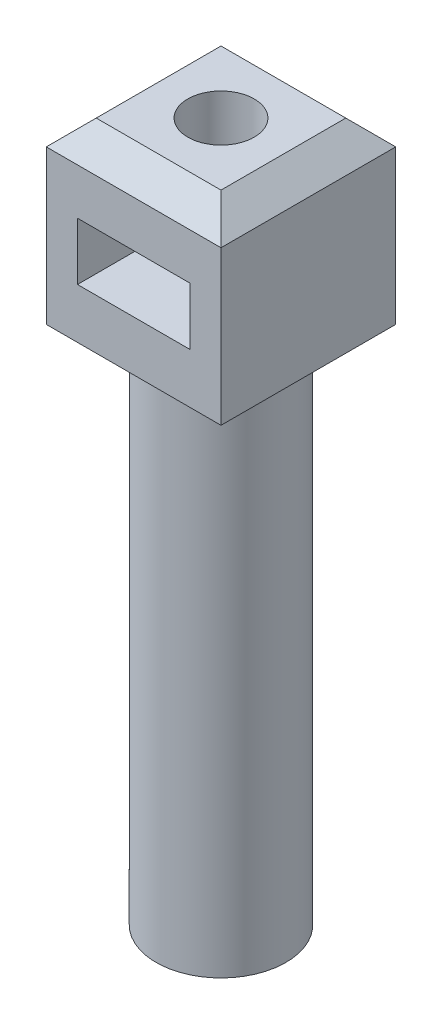
SolidWorks part; units mm, degrees
ref_plane "Front Plane" through (0, 0, 0) normal (0, 0, 1) x (1, 0, 0)
ref_plane "Top Plane" through (0, 0, 0) normal (0, 1, 0) x (1, 0, 0)
ref_plane "Right Plane" through (0, 0, 0) normal (1, 0, 0) x (0, 0, -1)
sketch "Sketch1" plane through (0, 0, 0) normal (0, 1, 0) x (1, 0, 0)
  circle A0 centre (0, 0) radius 6.604
  dimension "D1" = 13.208
extrude "Boss-Extrude1" add sketch "Sketch1" along normal blind 63.5
sketch "Sketch4" plane through (0, 0, 0) normal (0, -1, 0) x (1, 0, 0)
  line L1 (-12.7, -12.7) -> (12.7, -12.7)
  line L2 (-12.7, -12.7) -> (-12.7, 12.7)
  line L3 (-12.7, 12.7) -> (12.7, 12.7)
  line L4 (12.7, -12.7) -> (12.7, 12.7)
  line L5 (-12.7, -12.7) -> (12.7, 12.7) construction
  line L6 (-12.7, 12.7) -> (12.7, -12.7) construction
  point P0 (0, 0)
  dimension "D1" = 25.4
  dimension "D2" = 25.4
extrude "Boss-Extrude2" add sketch "Sketch4" along normal blind 1.27
ref_axis "Axis2" through (0, 63.5, 0) along (0, -1, 0)
ref_plane "Plane2" through (0, 50.8, 0) normal (0, 1, 0) x (1, 0, 0)
sketch "Sketch9" plane through (0, 50.8, 0) normal (0, 1, 0) x (1, 0, 0)
  line L1 (-8.89, -8.89) -> (8.89, -8.89)
  line L2 (-8.89, -8.89) -> (-8.89, 8.89)
  line L3 (-8.89, 8.89) -> (8.89, 8.89)
  line L4 (8.89, -8.89) -> (8.89, 8.89)
  line L5 (-8.89, -8.89) -> (8.89, 8.89) construction
  line L6 (-8.89, 8.89) -> (8.89, -8.89) construction
  point P0 (0, 0)
  dimension "D1" = 17.78
  dimension "D2" = 17.78
extrude "Boss-Extrude4" add sketch "Sketch9" along normal blind 20.32
sketch "Sketch10" plane through (0, 0, 8.89) normal (0, 0, 1) x (1, 0, 0)
  line L0 (0, 63.5) -> (0, 0) construction
  line L1 (-5.715, 58.039) -> (5.715, 58.039)
  line L2 (-5.715, 58.039) -> (-5.715, 63.881)
  line L3 (-5.715, 63.881) -> (5.715, 63.881)
  line L4 (5.715, 58.039) -> (5.715, 63.881)
  line L5 (-5.715, 58.039) -> (5.715, 63.881) construction
  line L6 (-5.715, 63.881) -> (5.715, 58.039) construction
  line L7 (-8.89, 71.12) -> (8.89, 71.12) construction
  line L8 (-8.89, 50.8) -> (8.89, 50.8) construction
  point P0 (0, 60.96)
  dimension "D1" = 11.43
  dimension "D2" = 5.842
  dimension "D3" = 7.239
  dimension "D4" = 7.239
extrude "Cut-Extrude2" cut sketch "Sketch10" against normal through all both and the other way through all
chamfer "Chamfer2" distance 2.54 angle 40 4 edges at (0, 50.8, -8.89) (-8.89, 50.8, 0) (8.89, 50.8, 0) (0, 50.8, 8.89) first distance on face at (0, 50.8, 0)
sketch "Sketch13" plane through (0, -1.27, 0) normal (0, -1, 0) x (1, 0, 0)
  line L1 (-12.7, 12.7) -> (12.7, 12.7)
  line L2 (-12.7, 12.7) -> (-12.7, -12.7)
  line L3 (-12.7, -12.7) -> (12.7, -12.7)
  line L4 (12.7, 12.7) -> (12.7, -12.7)
extrude "Cut-Extrude3" cut sketch "Sketch13" against normal blind 1.27
hole_wizard "1/4 Clearance Hole1" positions "Sketch16" profile "Sketch15" hole size "1/4" standard "ANSI Inch" end condition up to next
sketch "Sketch16" plane through (0, 71.12, 0) normal (0, 1, 0) x (1, 0, 0)
  point P0 (0, 0)
sketch "Sketch15" plane through (0, 71.12, 0) normal (1, 0, 0) x (0, 0, 1)
  line L0 (0, 0) -> (0, 7.239)
  line L1 (0, 7.239) -> (3.3782, 7.239)
  line L2 (3.3782, 7.239) -> (3.3782, 0)
  line L5 (3.3782, 0) -> (0, 0)
  line L11 (0, -6.35) -> (0, 107.95) construction
  dimension "Thru Hole Dia." = 6.7564
  dimension "Thru Hole Depth" = 7.239
chamfer "Chamfer3" distance 2.54 angle 45 1 edges at (8.89, 71.12, 0)
chamfer "Chamfer4" distance 2.54 angle 45 3 edges at (-1.27, 71.12, -8.89) (-8.89, 71.12, 0) (-1.27, 71.12, 8.89)
